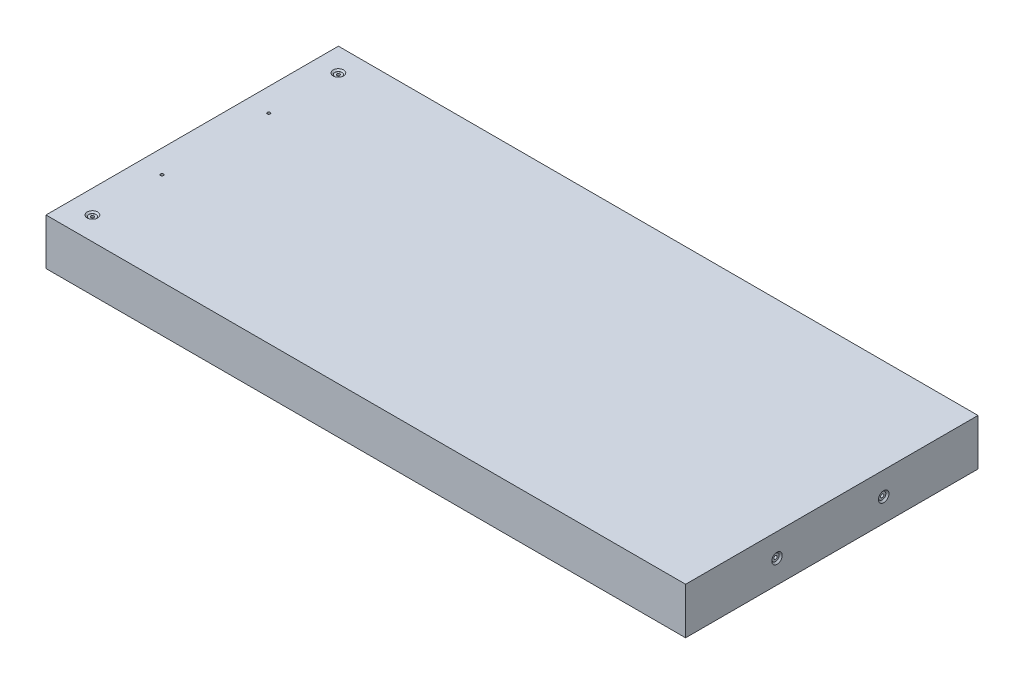
SolidWorks part; units mm, degrees
ref_plane "Front Plane" through (0, 0, 0) normal (0, 0, 1) x (1, 0, 0)
ref_plane "Top Plane" through (0, 0, 0) normal (0, 1, 0) x (1, 0, 0)
ref_plane "Right Plane" through (0, 0, 0) normal (1, 0, 0) x (0, 0, -1)
sketch "Sketch1" plane through (0, 0, 0) normal (0, 1, 0) x (1, 0, 0)
  line L1 (-175, 80) -> (175, 80)
  line L2 (-175, 80) -> (-175, -80)
  line L3 (-175, -80) -> (175, -80)
  line L4 (175, 80) -> (175, -80)
  line L5 (-175, 80) -> (175, -80) construction
  line L6 (-175, -80) -> (175, 80) construction
  point P0 (0, 0)
  dimension "D1" = 350
  dimension "D2" = 160
extrude "Boss-Extrude1" add sketch "Sketch1" along normal blind 25.4
hole_wizard "CBORE for #0 Binding Head Machine Screw3" positions "Sketch2" profile "Sketch3" counterbore size "#0" standard "ANSI Inch"
sketch "Sketch2" plane through (175, 0, 0) normal (1, 0, 0) x (0, 0, -1)
  line L0 (-80, 25.4) -> (-80, 0) construction
  point P0 (-30, 12.7)
  point P2 (28.4, 12.7)
  point P11 (-80, 12.7)
  dimension "D1" = 58.4
  dimension "D2" = 50
sketch "Sketch3" plane through (175, 12.7, 30) normal (0, 1, 0) x (0, 0, -1)
  line L0 (0, 0) -> (0, 30.5342)
  line L1 (0, 30.5342) -> (0.889, 30)
  line L2 (0.889, 30) -> (0.889, 0.8128)
  line L3 (0.889, 0.8128) -> (1.985, 0.8128)
  line L5 (1.985, 0.8128) -> (1.985, 0.8725)
  line L6 (1.985, 0.8725) -> (2.8575, 0)
  line L7 (2.8575, 0) -> (0, 0)
  line L8 (-1.985, 0.8725) -> (-2.8575, 0) construction
  line L10 (0, 30.5342) -> (-0.889, 30) construction
  line L11 (0, -6.35) -> (0, 107.95) construction
  dimension "Hole Dia." = 1.778
  dimension "Hole Depth" = 30
  dimension "C'Bore Dia." = 3.97
  dimension "C'Bore Depth" = 0.8128
  dimension "Near C'Sink Dia." = 5.715
  dimension "Near C'Sink Angle" = 90
  dimension "Drill Angle" = 118
hole_wizard "CBORE for #0 Binding Head Machine Screw1" positions "Sketch6" profile "Sketch7" counterbore size "#0" standard "ANSI Inch" end condition through all
sketch "Sketch6" plane through (0, 25.4, 0) normal (0, 1, 0) x (1, 0, 0)
  line L0 (-175, -80) -> (175, -80) construction
  line L1 (-175, 80) -> (-175, -80) construction
  line L2 (175, 80) -> (-175, 80) construction
  point P0 (-162.3, -67.3)
  point P2 (-162.3, 67.3)
  dimension "D1" = 12.7
  dimension "D2" = 12.7
  dimension "D3" = 12.7
sketch "Sketch7" plane through (-162.3, 25.4, 67.3) normal (1, 0, 0) x (0, 0, 1)
  line L0 (0, 0) -> (0, 25.4)
  line L1 (0, 25.4) -> (0.8064, 25.4)
  line L3 (0.8064, 25.4) -> (0.8065, 0.8128)
  line L4 (1.985, 0.8128) -> (0.8065, 0.8128)
  line L5 (1.985, 0.8128) -> (1.985, 0.7321)
  line L6 (1.985, 0.7321) -> (2.8575, 0)
  line L7 (2.8575, 0) -> (0, 0)
  line L8 (-1.985, 0.7321) -> (-2.8575, 0) construction
  line L11 (0, -6.35) -> (0, 107.95) construction
  dimension "Thru Hole Dia." = 1.6129
  dimension "Thru Hole Depth" = 25.4
  dimension "C'Bore Dia." = 3.97
  dimension "C'Bore Depth" = 0.8128
  dimension "Near C'Sink Dia." = 5.715
  dimension "Near C'Sink Angle" = 100
hole_wizard "CBORE for #0 Binding Head Machine Screw2" positions "Sketch8" profile "Sketch9" counterbore size "#0" standard "ANSI Inch" end condition through all
sketch "Sketch8" plane through (0, 0, 0) normal (0, -1, 0) x (-1, 0, 0)
  line L0 (-175, 80) -> (175, 80) construction
  line L1 (175, -80) -> (-175, -80) construction
  line L2 (175, 80) -> (175, -80) construction
  point P0 (162.3, 29.2)
  point P2 (162.3, -29.2)
  dimension "D1" = 50.8
  dimension "D2" = 50.8
  dimension "D3" = 12.7
  dimension "D4" = 12.7
sketch "Sketch9" plane through (-162.3, 0, -29.2) normal (1, 0, 0) x (0, 0, -1)
  line L0 (0, 0) -> (0, 25.4)
  line L1 (0, 25.4) -> (0.8064, 25.4)
  line L3 (0.8064, 25.4) -> (0.8065, 0.8128)
  line L4 (1.985, 0.8128) -> (0.8065, 0.8128)
  line L5 (1.985, 0.8128) -> (1.985, 0.7321)
  line L6 (1.985, 0.7321) -> (2.8575, 0)
  line L7 (2.8575, 0) -> (0, 0)
  line L8 (-1.985, 0.7321) -> (-2.8575, 0) construction
  line L11 (0, -6.35) -> (0, 107.95) construction
  dimension "Thru Hole Dia." = 1.6129
  dimension "Thru Hole Depth" = 25.4
  dimension "C'Bore Dia." = 3.97
  dimension "C'Bore Depth" = 0.8128
  dimension "Near C'Sink Dia." = 5.715
  dimension "Near C'Sink Angle" = 100
